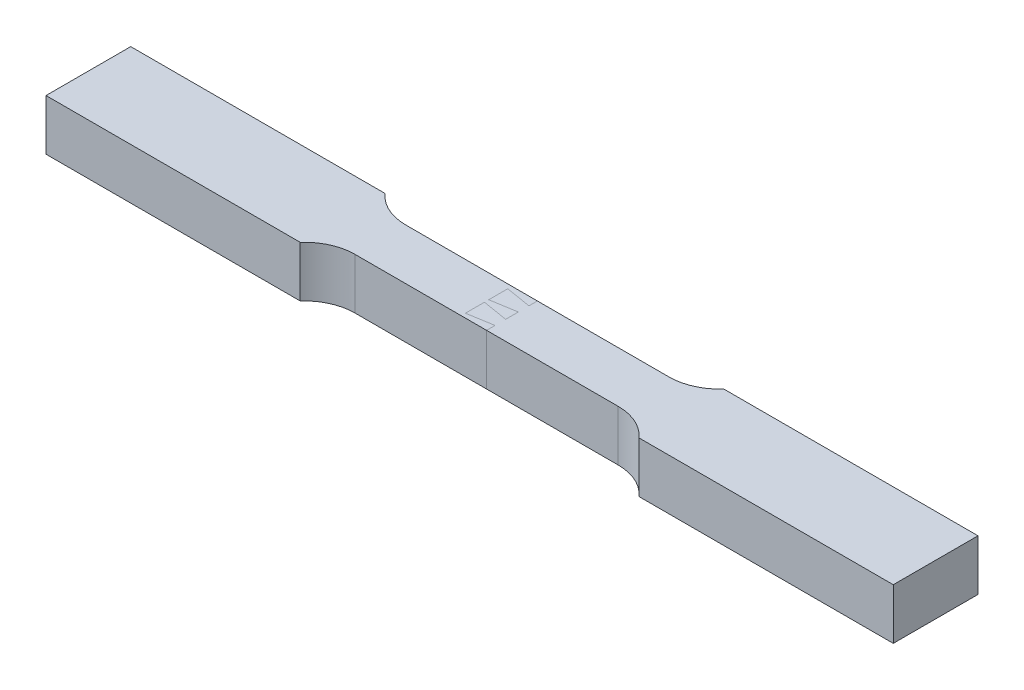
SolidWorks part; units mm, degrees
ref_plane "Front" through (0, 0, 0) normal (0, 0, 1) x (1, 0, 0)
ref_plane "Top" through (0, 0, 0) normal (0, 1, 0) x (1, 0, 0)
ref_plane "Right" through (0, 0, 0) normal (1, 0, 0) x (0, 0, -1)
sketch "Sketch1" plane through (0, 0, 0) normal (0, 1, 0) x (1, 0, 0)
  line L0 (0, 32.0696) -> (0, -21.7429) construction
  line L2 (15.5279, -3) -> (-15.5279, -3)
  line L4 (-20, 5) -> (-50, 5)
  line L5 (-50, 5) -> (-50, -5)
  line L6 (-50, -5) -> (-20, -5)
  line L8 (-15.5279, 3) -> (15.5279, 3)
  line L10 (0, 2) -> (-3, 2.5)
  line L11 (-3, 2.5) -> (-3, 0.25)
  line L12 (-50, 0) -> (50, 0) construction
  line L13 (0, 0) -> (40.1021, 0) construction
  line L14 (-3, 0.25) -> (0, 0.75)
  line L15 (0, 0.75) -> (0, -0.75)
  line L17 (-3, 1.375) -> (0.5856, 1.375) construction
  line L18 (-3, -0.25) -> (0, -0.75)
  line L19 (-3, -2.5) -> (-3, -0.25)
  line L20 (0, -2) -> (-3, -2.5)
  line L21 (0, 3) -> (0, 2)
  line L22 (0, -2) -> (0, -3)
  line L23 (50, 5) -> (50, -5)
  line L24 (50, -5) -> (20, -5)
  line L25 (20, 5) -> (50, 5)
  arc A0 (-15.5279, 3) -> (-20, 5) centre (-15.5279, 9) cw
  arc A1 (-15.5279, -3) -> (-20, -5) centre (-15.5279, -9) ccw
  arc A2 (15.5279, -3) -> (20, -5) centre (15.5279, -9) cw
  arc A3 (15.5279, 3) -> (20, 5) centre (15.5279, 9) ccw
  dimension "D8" = 2.25
  dimension "D11" = 6
  dimension "D12" = 6
  dimension "D2" = 0.5
  dimension "D3" = 10
  dimension "D4" = 3
  dimension "D5" = 1.25
  dimension "D6" = 50
  dimension "D7" = 30
extrude "Boss-Extrude1" add sketch "Sketch1" along normal blind 6 contours L8 L2 L4 L5 L6 region at (-28.402, 0, 0)
extrude "Boss-Extrude3" add sketch "Sketch1<4>" along normal blind 6 separate body contours A3 L8 L21 L10 L11 L14 L15 L18 L19 L20 L22 L2 A2 L24 L23 L25 region at (27.034, 0, 0)
sketch "Sketch1<4>" plane through (0, 0, 0) normal (0, 1, 0) x (1, 0, 0) same geometry as "Sketch1"
equation "\"SectionLength\"=10"
equation "\"IntermediateLength\"=12.5"
equation "\"TotalLength\"=15"
equation "\"TotalWidth\"=8"
equation "\"DovetailRadius\"=0.25"
